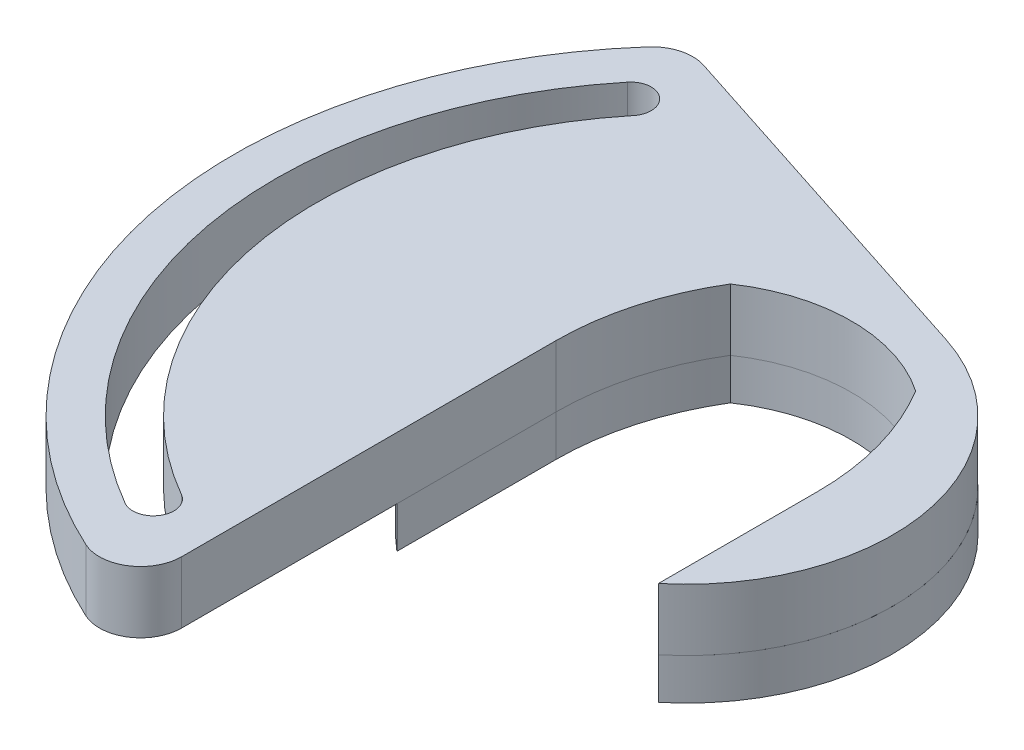
SolidWorks part; units mm, degrees
material "ABS"
ref_plane "Front Plane" through (0, 0, 0) normal (0, 0, 1) x (1, 0, 0)
ref_plane "Top Plane" through (0, 0, 0) normal (0, 1, 0) x (1, 0, 0)
ref_plane "Right Plane" through (0, 0, 0) normal (1, 0, 0) x (0, 0, -1)
sketch "Sketch1" plane through (0, 0, 0) normal (0, 1, 0) x (1, 0, 0)
  line L0 (0, -8) -> (0, 8) construction
  line L1 (-6.35, 0) -> (6.35, 0) construction
  line L2 (-6.35, 0) -> (-6.35, -7.7251)
  line L3 (6.35, -7.7251) -> (6.35, 0)
  arc A0 (-4.5, 6.6144) -> (4.5, 6.6144) centre (0, 0) cw
  arc A1 (-4.5, -6.6144) -> (4.5, -6.6144) centre (0, 0) ccw construction
  arc A2 (-4.5, 6.6144) -> (-4.5, -6.6144) centre (6.3993, 0) ccw construction
  arc A3 (-4.5, 6.6144) -> (-6.35, 0) centre (6.3993, 0) ccw
  arc A4 (4.5, 6.6144) -> (6.35, 0) centre (-6.3993, 0) cw
  arc A5 (-6.35, -7.7251) -> (6.35, -7.7251) centre (0, 0) cw
  dimension "D4" = 2
  dimension "D1" = 12.7
  dimension "D2" = 8
  dimension "D3" = 4.5
extrude "Boss-Extrude1" add sketch "Sketch1" along normal blind 2
sketch "Sketch2" plane through (0, 2, 0) normal (0, 1, 0) x (1, 0, 0)
  line L0 (3.0842, 9.5125) -> (-15.5563, 15.5563)
  line L4 (-6.35, -21.0637) -> (-6.35, -7.7251)
  line L5 (0, 0) -> (-15.5563, 15.5563) construction
  line L7 (0, 0) -> (0, -7.7251) construction
  line L10 (-6.35, -7.7251) -> (-6.35, 0)
  line L11 (6.35, 0) -> (6.35, -7.7251)
  line L12 (-6.35, -7.7251) -> (-6.35, 0)
  line L13 (6.35, 0) -> (6.35, -7.7251)
  arc A6 (-6.35, -21.0637) -> (-15.5563, 15.5563) centre (0, 0) cw
  arc A7 (6.35, -7.7251) -> (-6.35, -7.7251) centre (0, 0) ccw construction
  arc A8 (6.35, -7.7251) -> (3.0842, 9.5125) centre (0, 0) ccw
  arc A12 (6.35, -7.7251) -> (-6.35, -7.7251) centre (0, 0) ccw
  arc A13 (6.35, 0) -> (4.5, 6.6144) centre (-6.3993, 0) ccw
  arc A14 (4.5, 6.6144) -> (-4.5, 6.6144) centre (0, 0) ccw
  arc A15 (-4.5, 6.6144) -> (-6.35, 0) centre (6.3993, 0) ccw
  arc A17 (6.35, 0) -> (4.5, 6.6144) centre (-6.3993, 0) ccw
  arc A18 (4.5, 6.6144) -> (-4.5, 6.6144) centre (0, 0) ccw
  arc A19 (-4.5, 6.6144) -> (-6.35, 0) centre (6.3993, 0) ccw
  dimension "D1" = 22
  dimension "D2" = 135
  dimension "D3" = 0
extrude "Boss-Extrude2" add sketch "Sketch2" along normal blind 3 separate body
fillet "Fillet1" radius 2 2 edges at (-6.35, 3.5, 21.0637) (-15.5563, 3.5, -15.5563)
ref_axis "Axis1" through (0, -0.25, 0) along (0, 1, 0)
sketch "Sketch3" plane through (0, 5, 0) normal (0, 1, 0) x (1, 0, 0)
  line L0 (-17.6684, -3.2592) -> (-18.6518, -3.4406) construction
  line L1 (-19.6352, -3.6221) -> (-18.6518, -3.4406) construction
  arc A0 (-9.463, -16.4371) -> (-14.7048, 11.9789) centre (0, 0) cw construction
  arc A1 (-8.9641, -15.5705) -> (-9.9619, -17.3037) centre (-9.463, -16.4371) cw
  arc A2 (-15.4801, 12.6105) -> (-13.9295, 11.3473) centre (-14.7048, 11.9789) cw
  arc A3 (-15.4801, 12.6105) -> (-9.9619, -17.3037) centre (0, 0) ccw
  arc A4 (-13.9295, 11.3473) -> (-8.9641, -15.5705) centre (0, 0) ccw
  dimension "D1" = 1
  dimension "D2" = 1
  dimension "D3" = 1
extrude "Cut-Extrude1" cut sketch "Sketch3" against normal through all
sketch "Sketch4" plane through (0, 2, 0) normal (0, -1, 0) x (1, 0, 0)
  arc A0 (-9.463, 16.4371) -> (-14.7048, -11.9789) centre (0, 0) ccw construction
  arc A1 (-9.463, 16.4371) -> (-14.7048, -11.9789) centre (0, 0) ccw
